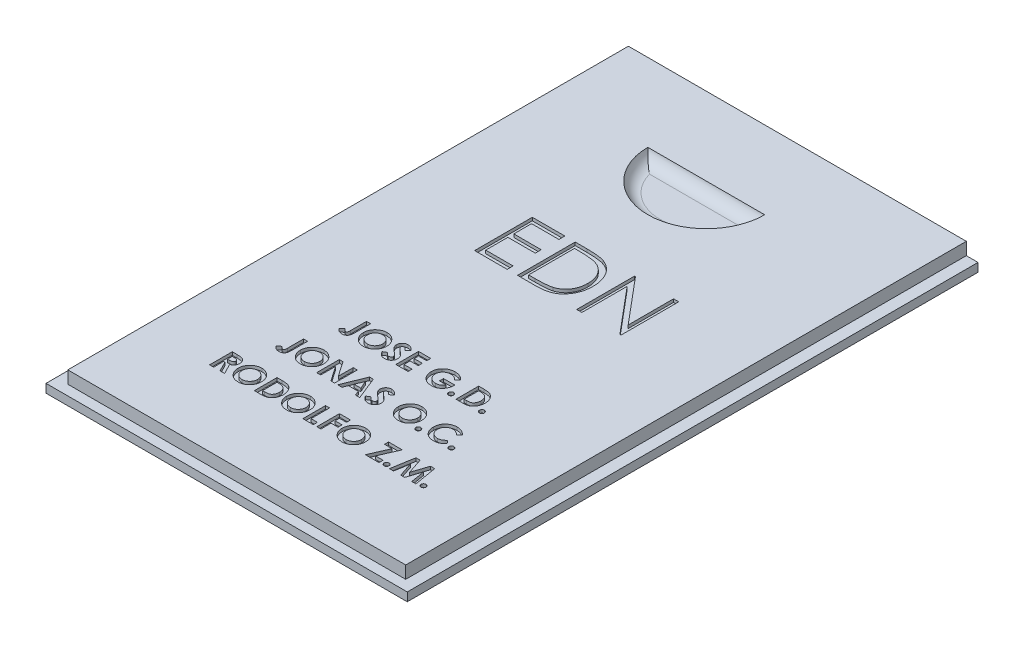
SolidWorks part; units mm, degrees
ref_plane "Front Plane" through (0, 0, 0) normal (0, 0, 1) x (1, 0, 0)
ref_plane "Top Plane" through (0, 0, 0) normal (0, 1, 0) x (1, 0, 0)
ref_plane "Right Plane" through (0, 0, 0) normal (1, 0, 0) x (0, 0, -1)
sketch "Croquis1" plane through (0, 0, 0) normal (0, 0, 1) x (1, 0, 0)
  line L0 (-23.2, 0) -> (-23.2, 1.1)
  line L1 (-23.2, 1.1) -> (-21.7, 1.1)
  line L2 (-21.7, 1.1) -> (-21.7, 2.7)
  line L3 (-21.7, 2.7) -> (21.7, 2.7)
  line L4 (21.7, 2.7) -> (21.7, 1.1)
  line L5 (21.7, 1.1) -> (23.2, 1.1)
  line L6 (23.2, 1.1) -> (23.2, 0)
  line L7 (23.2, 0) -> (-23.2, 0)
  point P2 (0, 0)
  dimension "D1" = 1.5
  dimension "D2" = 1.5
  dimension "D3" = 46.4
  dimension "D4" = 1.1
  dimension "D5" = 1.1
  dimension "D6" = 1.6
extrude "Saliente-Extruir1" add sketch "Croquis1" along normal blind 72
sketch "Croquis2" plane through (0, 0, 72) normal (0, 0, 1) x (1, 0, 0)
  line L0 (23.2, 1.1) -> (23.2, 0)
  line L1 (23.2, 0) -> (-23.2, 0)
  line L2 (-23.2, 0) -> (-23.2, 1.1)
  line L3 (-23.2, 1.1) -> (23.2, 1.1)
extrude "Saliente-Extruir2" add sketch "Croquis2" along normal blind 1.3
sketch "Croquis3" plane through (0, 2.7, 0) normal (0, 1, 0) x (1, 0, 0)
  line L0 (-9.2, -10) -> (5.8, -10)
  line L1 (21.7, 0) -> (-21.7, 0) construction
  line L2 (-21.7, -72) -> (-21.7, 0) construction
  arc A0 (-9.2, -10) -> (5.8, -10) centre (-1.7, -10) ccw
  dimension "D1" = 15
  dimension "D2" = 10
  dimension "D3" = 20
extrude "Cortar-Extruir1" cut sketch "Croquis3" against normal blind 1.3
fillet "Redondeo4" radius 1.6 2 edges at (-1.7, 1.4, 10) (-1.7, 1.4, 17.5)
sketch "Croquis5" plane through (0, 2.7, 0) normal (0, 1, 0) x (1, 0, 0)
  line L0 (-11.2577, -32.6059) -> (12.3755, -32.6059) construction
  line L1 (-17.0258, -50.3328) -> (18.1435, -50.3328) construction
  line L2 (-17.0258, -56.3328) -> (18.1435, -56.3328) construction
  line L3 (-17.0258, -62.3328) -> (18.1435, -62.3328) construction
  line L4 (21.7, 0) -> (-21.7, 0) construction
  text T0 "EDN" font "Century Gothic" height in points 28
  text T1 "JOSE G.D." font "Century Gothic" height in points 11
  text T2 "JONAS O.C." font "Century Gothic" height in points 11
  text T3 "RODOLFO Z.M." font "Century Gothic" height in points 11
  point P8 (0.5589, -50.3328)
  point P9 (0.5589, -56.3328)
  point P10 (0.5589, -62.3328)
  dimension "D1" = 32.6059
  dimension "D2" = 6
  dimension "D3" = 6
  dimension "D4" = 50.3328
extrude "Cortar-Extruir5" cut sketch "Croquis5" against normal blind 0.4
sketch "Croquis6" plane through (0, 0, 0) normal (0, -1, 0) x (1, 0, 0)
  line L0 (3.2, 1.9) -> (3.2, 0.9)
  line L1 (3.2, 1.9) -> (-3.2, 1.9)
  line L2 (3.2, 0.9) -> (-3.2, 0.9)
  line L3 (-3.2, 1.9) -> (-3.2, 0.9)
  line L4 (3.2, 1.9) -> (-3.2, 0.9) construction
  line L5 (3.2, 0.9) -> (-3.2, 1.9) construction
  line L6 (-23.2, 0) -> (23.2, 0) construction
  point P1 (0, 1.4)
  dimension "D1" = 0.9
  dimension "D2" = 1
  dimension "D3" = 6.4
extrude "Saliente-Extruir3" add sketch "Croquis6" along normal blind 0.35
fillet "Redondeo11" radius 0.3 4 edges at (3.2, -0.35, 1.4) (0, -0.35, 0.9) (-3.2, -0.35, 1.4) (0, -0.35, 1.9)
